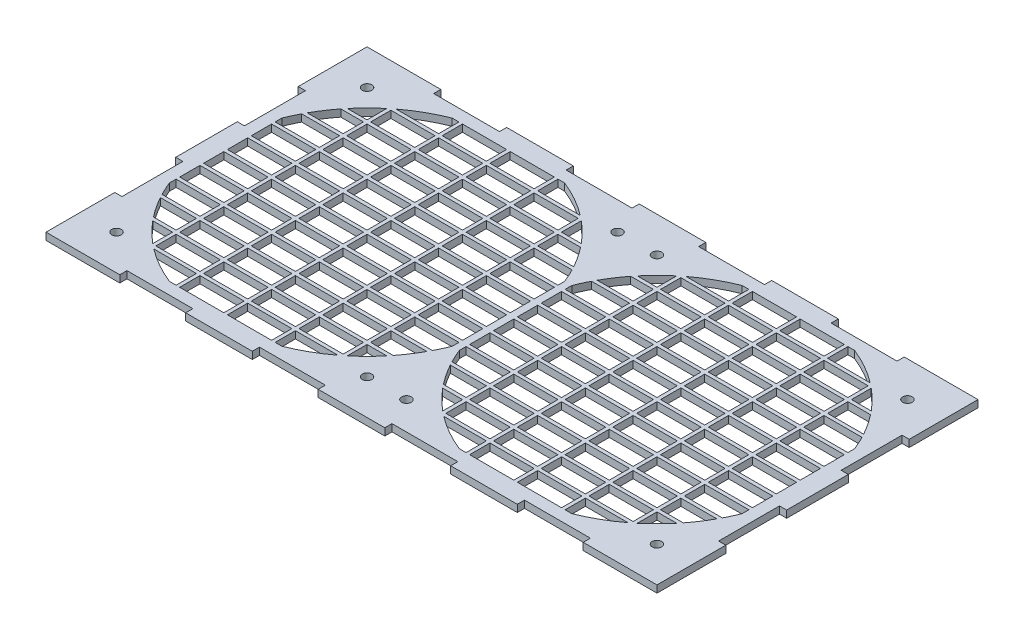
SolidWorks part; units mm, degrees
ref_plane "Front Plane" through (0, 0, 0) normal (0, 0, 1) x (1, 0, 0)
ref_plane "Top Plane" through (0, 0, 0) normal (0, 1, 0) x (1, 0, 0)
ref_plane "Right Plane" through (0, 0, 0) normal (1, 0, 0) x (0, 0, -1)
sketch "Sketch1" plane through (0, 0, 0) normal (0, 1, 0) x (1, 0, 0)
  line L0 (-60.65, 0) -> (0, 0) construction
  line L1 (0, 0) -> (60.65, 0) construction
  line L2 (-119.8, 23.5074) -> (-124.8, 23.5074) construction
  line L3 (-37.1426, -59.15) -> (-84.1574, -59.15)
  line L4 (-1.5, -23.5074) -> (-1.5, 23.5074)
  line L5 (-37.1426, 59.15) -> (-84.1574, 59.15)
  line L6 (-119.8, -23.5074) -> (-119.8, 23.5074)
  line L7 (-1.5, -59.15) -> (-119.8, 59.15) construction
  line L8 (-1.5, 59.15) -> (-119.8, -59.15) construction
  line L9 (84.1574, -59.15) -> (37.1426, -59.15)
  line L10 (119.8, -23.5074) -> (119.8, 23.5074)
  line L11 (84.1574, 59.15) -> (37.1426, 59.15)
  line L12 (1.5, -23.5074) -> (1.5, 23.5074)
  line L13 (119.8, -59.15) -> (1.5, 59.15) construction
  line L14 (119.8, 59.15) -> (1.5, -59.15) construction
  line L15 (96.9333, -64.15) -> (69.3667, -64.15)
  line L16 (124.8, -38.37) -> (124.8, -12.89)
  line L17 (96.9333, 64.15) -> (69.3667, 64.15)
  line L18 (-124.8, -38.37) -> (-124.8, -12.89)
  line L19 (124.8, -64.15) -> (-124.8, 64.15) construction
  line L20 (124.8, 64.15) -> (-132.4261, -68.07) construction
  line L21 (-84.1574, 64.15) -> (-84.1574, 59.15) construction
  line L22 (-69.3667, 64.15) -> (-96.9333, 64.15)
  line L25 (-124.8, 67.15) -> (-96.9333, 67.15)
  line L26 (-96.9333, 64.15) -> (-96.9333, 67.15)
  line L28 (-69.3667, 64.15) -> (-69.3667, 67.15)
  line L29 (-69.3667, 67.15) -> (-41.5, 67.15)
  line L30 (-41.5, 64.15) -> (-41.5, 67.15)
  line L32 (-13.9333, 64.15) -> (-13.9333, 67.15)
  line L33 (-13.9333, 67.15) -> (13.9333, 67.15)
  line L34 (13.9333, 64.15) -> (13.9333, 67.15)
  line L36 (41.5, 64.15) -> (41.5, 67.15)
  line L37 (41.5, 67.15) -> (69.3667, 67.15)
  line L38 (69.3667, 64.15) -> (69.3667, 67.15)
  line L41 (124.8, 67.15) -> (96.9333, 67.15)
  line L42 (96.9333, 64.15) -> (96.9333, 67.15)
  line L43 (-13.9333, 64.15) -> (-41.5, 64.15)
  line L44 (41.5, 64.15) -> (13.9333, 64.15)
  line L45 (-124.8, 65.65) -> (-97.2333, 65.65) construction
  line L46 (-97.2333, 65.65) -> (-96.9333, 65.65) construction
  line L47 (-69.3667, -64.15) -> (-96.9333, -64.15)
  line L50 (-124.8, -67.15) -> (-96.9333, -67.15)
  line L51 (-96.9333, -64.15) -> (-96.9333, -67.15)
  line L53 (-69.3667, -64.15) -> (-69.3667, -67.15)
  line L54 (-69.3667, -67.15) -> (-41.5, -67.15)
  line L55 (-41.5, -64.15) -> (-41.5, -67.15)
  line L57 (-13.9333, -64.15) -> (-13.9333, -67.15)
  line L58 (-13.9333, -67.15) -> (13.9333, -67.15)
  line L59 (13.9333, -64.15) -> (13.9333, -67.15)
  line L61 (41.5, -64.15) -> (41.5, -67.15)
  line L62 (41.5, -67.15) -> (69.3667, -67.15)
  line L63 (69.3667, -64.15) -> (69.3667, -67.15)
  line L65 (96.9333, -64.15) -> (96.9333, -67.15)
  line L66 (96.9333, -67.15) -> (124.8, -67.15)
  line L68 (-13.9333, -64.15) -> (-41.5, -64.15)
  line L69 (41.5, -64.15) -> (13.9333, -64.15)
  line L70 (-124.8, 64.15) -> (-124.8, 65.65) construction
  line L71 (-124.8, 67.15) -> (-127.8, 67.15)
  line L73 (-124.8, 38.37) -> (-127.8, 38.37)
  line L74 (-127.8, 67.15) -> (-127.8, 38.37)
  line L75 (-124.8, 12.89) -> (-127.8, 12.89)
  line L77 (-124.8, -12.89) -> (-127.8, -12.89)
  line L78 (-127.8, 12.89) -> (-127.8, -12.89)
  line L79 (-124.8, -67.15) -> (-127.8, -67.15)
  line L81 (-124.8, -38.37) -> (-127.8, -38.37)
  line L82 (-127.8, -67.15) -> (-127.8, -38.37)
  line L83 (124.8, -67.15) -> (127.8, -67.15)
  line L85 (124.8, -38.37) -> (127.8, -38.37)
  line L87 (124.8, -12.89) -> (127.8, -12.89)
  line L89 (124.8, 12.89) -> (127.8, 12.89)
  line L90 (127.8, -12.89) -> (127.8, 12.89)
  line L91 (124.8, 38.37) -> (127.8, 38.37)
  line L95 (-124.8, 65.65) -> (-124.8, 67.15) construction
  line L96 (-124.8, 12.89) -> (-124.8, 38.37)
  line L97 (124.8, 12.89) -> (124.8, 38.37)
  line L98 (124.8, 67.15) -> (127.8, 67.15)
  line L99 (-60.65, -64.15) -> (-60.65, -59.15) construction
  line L100 (124.8, 64.15) -> (124.8, 38.67) construction
  line L101 (124.8, 38.67) -> (124.8, 38.37) construction
  line L102 (127.8, 38.37) -> (127.8, 64.15)
  line L103 (127.8, 64.15) -> (127.8, 67.15)
  line L104 (124.8, 0) -> (119.8, 0) construction
  line L105 (127.8, -67.15) -> (127.8, -64.15)
  line L106 (127.8, -64.15) -> (127.8, -38.37)
  arc A1 (-119.8, -23.5074) -> (-84.1574, -59.15) centre (-60.65, 0) ccw
  arc A2 (-84.1574, 59.15) -> (-119.8, 23.5074) centre (-60.65, 0) ccw
  arc A3 (1.5, -23.5074) -> (37.1426, -59.15) centre (60.65, 0) ccw
  arc A4 (-1.5, 23.5074) -> (-37.1426, 59.15) centre (-60.65, 0) ccw
  arc A5 (37.1426, 59.15) -> (1.5, 23.5074) centre (60.65, 0) ccw
  arc A6 (119.8, 23.5074) -> (84.1574, 59.15) centre (60.65, 0) ccw
  arc A7 (84.1574, -59.15) -> (119.8, -23.5074) centre (60.65, 0) ccw
  arc A8 (-37.1426, -59.15) -> (-1.5, -23.5074) centre (-60.65, 0) ccw
  point P96 (124.8, -64.15)
  point P98 (0, 0)
  point P101 (124.8, 62.2393)
  point P103 (-127.8, -5.5733)
  point P104 (-127.8, -41.7742)
  dimension "D3" = 127.3
  dimension "D1" = 118.3
  dimension "D2" = 3
  dimension "D4" = 5
  dimension "D5" = 45
  dimension "D6" = 0.3
  dimension "D7" = 3
extrude "Boss-Extrude1" add sketch "Sketch1" along normal blind 3
sketch "Sketch2" plane through (0, 3, 0) normal (0, 1, 0) x (1, 0, 0)
  line L0 (-124.8, 38.37) -> (-124.8, 12.89) construction
  line L1 (-124.8, 60.65) -> (124.8, 60.65)
  line L2 (-124.8, 60.65) -> (-124.8, 59.15)
  line L3 (-124.8, 59.15) -> (124.8, 59.15)
  line L4 (124.8, 60.65) -> (124.8, 59.15)
  line L5 (124.8, 12.89) -> (124.8, 38.37) construction
  line L6 (-37.1426, 59.15) -> (-84.1574, 59.15) construction
  line L7 (-124.8, 50.6667) -> (-124.8, 49.1667)
  line L8 (-124.8, 50.6667) -> (124.8, 50.6667)
  line L9 (124.8, 50.6667) -> (124.8, 49.1667)
  line L10 (-124.8, 49.1667) -> (124.8, 49.1667)
  line L11 (-124.8, 40.6833) -> (-124.8, 39.1833)
  line L12 (-124.8, 40.6833) -> (124.8, 40.6833)
  line L13 (124.8, 40.6833) -> (124.8, 39.1833)
  line L14 (-124.8, 39.1833) -> (124.8, 39.1833)
  line L15 (-124.8, 30.7) -> (-124.8, 29.2)
  line L16 (-124.8, 30.7) -> (124.8, 30.7)
  line L17 (124.8, 30.7) -> (124.8, 29.2)
  line L18 (-124.8, 29.2) -> (124.8, 29.2)
  line L19 (-124.8, 20.7167) -> (-124.8, 19.2167)
  line L20 (-124.8, 20.7167) -> (124.8, 20.7167)
  line L21 (124.8, 20.7167) -> (124.8, 19.2167)
  line L22 (-124.8, 19.2167) -> (124.8, 19.2167)
  line L23 (-124.8, 10.7333) -> (-124.8, 9.2333)
  line L24 (-124.8, 10.7333) -> (124.8, 10.7333)
  line L25 (124.8, 10.7333) -> (124.8, 9.2333)
  line L26 (-124.8, 9.2333) -> (124.8, 9.2333)
  line L27 (-124.8, 0.75) -> (-124.8, -0.75)
  line L28 (-124.8, 0.75) -> (124.8, 0.75)
  line L29 (124.8, 0.75) -> (124.8, -0.75)
  line L30 (-124.8, -0.75) -> (124.8, -0.75)
  line L31 (-124.8, -9.2333) -> (-124.8, -10.7333)
  line L32 (-124.8, -9.2333) -> (124.8, -9.2333)
  line L33 (124.8, -9.2333) -> (124.8, -10.7333)
  line L34 (-124.8, -10.7333) -> (124.8, -10.7333)
  line L35 (-124.8, -19.2167) -> (-124.8, -20.7167)
  line L36 (-124.8, -19.2167) -> (124.8, -19.2167)
  line L37 (124.8, -19.2167) -> (124.8, -20.7167)
  line L38 (-124.8, -20.7167) -> (124.8, -20.7167)
  line L39 (-124.8, -29.2) -> (-124.8, -30.7)
  line L40 (-124.8, -29.2) -> (124.8, -29.2)
  line L41 (124.8, -29.2) -> (124.8, -30.7)
  line L42 (-124.8, -30.7) -> (124.8, -30.7)
  line L43 (-124.8, -39.1833) -> (-124.8, -40.6833)
  line L44 (-124.8, -39.1833) -> (124.8, -39.1833)
  line L45 (124.8, -39.1833) -> (124.8, -40.6833)
  line L46 (-124.8, -40.6833) -> (124.8, -40.6833)
  line L47 (-124.8, -49.1667) -> (-124.8, -50.6667)
  line L48 (-124.8, -49.1667) -> (124.8, -49.1667)
  line L49 (124.8, -49.1667) -> (124.8, -50.6667)
  line L50 (-124.8, -50.6667) -> (124.8, -50.6667)
  line L51 (-124.8, -59.15) -> (-124.8, -60.65)
  line L52 (-124.8, -59.15) -> (124.8, -59.15)
  line L53 (124.8, -59.15) -> (124.8, -60.65)
  line L54 (-124.8, -60.65) -> (124.8, -60.65)
  line L56 (-84.1574, -59.15) -> (-37.1426, -59.15) construction
  point P11 (-124.8, 59.15)
  point P59 (0, 0)
  dimension "D1" = 1.5
  dimension "D2" = 13
extrude "Boss-Extrude2" add sketch "Sketch2" against normal through all
sketch "Sketch3" plane through (0, 3, 0) normal (0, 1, 0) x (1, 0, 0)
  line L0 (0, 0) -> (0, 48.5777) construction
  line L1 (-119.8, 19.2167) -> (-119.8, 10.7333) construction
  line L2 (-119.8, -59.15) -> (-121.3, -59.15)
  line L3 (-119.8, -59.15) -> (-119.8, 59.15)
  line L4 (-119.8, 59.15) -> (-121.3, 59.15)
  line L5 (-121.3, -59.15) -> (-121.3, 59.15)
  line L6 (-37.1426, 59.15) -> (-84.1574, 59.15) construction
  line L7 (-84.1574, -59.15) -> (-37.1426, -59.15) construction
  line L8 (-99.8333, -59.15) -> (-99.8333, 59.15)
  line L9 (-99.8333, -59.15) -> (-101.3333, -59.15)
  line L10 (-101.3333, -59.15) -> (-101.3333, 59.15)
  line L11 (-99.8333, 59.15) -> (-101.3333, 59.15)
  line L12 (-79.8667, -59.15) -> (-79.8667, 59.15)
  line L13 (-79.8667, -59.15) -> (-81.3667, -59.15)
  line L14 (-81.3667, -59.15) -> (-81.3667, 59.15)
  line L15 (-79.8667, 59.15) -> (-81.3667, 59.15)
  line L16 (-59.9, -59.15) -> (-59.9, 59.15)
  line L17 (-59.9, -59.15) -> (-61.4, -59.15)
  line L18 (-61.4, -59.15) -> (-61.4, 59.15)
  line L19 (-59.9, 59.15) -> (-61.4, 59.15)
  line L20 (-39.9333, -59.15) -> (-39.9333, 59.15)
  line L21 (-39.9333, -59.15) -> (-41.4333, -59.15)
  line L22 (-41.4333, -59.15) -> (-41.4333, 59.15)
  line L23 (-39.9333, 59.15) -> (-41.4333, 59.15)
  line L24 (-19.9667, -59.15) -> (-19.9667, 59.15)
  line L25 (-19.9667, -59.15) -> (-21.4667, -59.15)
  line L26 (-21.4667, -59.15) -> (-21.4667, 59.15)
  line L27 (-19.9667, 59.15) -> (-21.4667, 59.15)
  line L28 (0, -59.15) -> (0, 59.15)
  line L29 (0, -59.15) -> (-1.5, -59.15)
  line L30 (-1.5, -59.15) -> (-1.5, 59.15)
  line L31 (0, 59.15) -> (-1.5, 59.15)
  line L48 (119.8, 59.15) -> (121.3, 59.15)
  line L49 (-1.5, -9.2333) -> (-1.5, -0.75) construction
  line L50 (121.3, -59.15) -> (121.3, 59.15)
  line L51 (119.8, -59.15) -> (121.3, -59.15)
  line L52 (119.8, -59.15) -> (119.8, 59.15)
  line L53 (-13.9333, -67.15) -> (13.9333, -67.15) construction
  line L54 (99.8333, 59.15) -> (101.3333, 59.15)
  line L55 (101.3333, -59.15) -> (101.3333, 59.15)
  line L56 (99.8333, -59.15) -> (101.3333, -59.15)
  line L57 (99.8333, -59.15) -> (99.8333, 59.15)
  line L58 (79.8667, 59.15) -> (81.3667, 59.15)
  line L59 (81.3667, -59.15) -> (81.3667, 59.15)
  line L60 (79.8667, -59.15) -> (81.3667, -59.15)
  line L61 (79.8667, -59.15) -> (79.8667, 59.15)
  line L62 (59.9, 59.15) -> (61.4, 59.15)
  line L63 (61.4, -59.15) -> (61.4, 59.15)
  line L64 (59.9, -59.15) -> (61.4, -59.15)
  line L65 (59.9, -59.15) -> (59.9, 59.15)
  line L66 (39.9333, 59.15) -> (41.4333, 59.15)
  line L67 (41.4333, -59.15) -> (41.4333, 59.15)
  line L68 (39.9333, -59.15) -> (41.4333, -59.15)
  line L69 (39.9333, -59.15) -> (39.9333, 59.15)
  line L70 (19.9667, 59.15) -> (21.4667, 59.15)
  line L71 (21.4667, -59.15) -> (21.4667, 59.15)
  line L72 (19.9667, -59.15) -> (21.4667, -59.15)
  line L73 (19.9667, -59.15) -> (19.9667, 59.15)
  line L74 (0, 59.15) -> (1.5, 59.15)
  line L75 (1.5, -59.15) -> (1.5, 59.15)
  line L76 (0, -59.15) -> (1.5, -59.15)
  line L77 (0, -59.15) -> (0, 59.15)
  line L78 (1.5, 19.2167) -> (1.5, 10.7333) construction
  point P45 (0, -67.15)
  dimension "D2" = 1.5
  dimension "D1" = 7
  dimension "D3" = 7
extrude "Boss-Extrude3" add sketch "Sketch3" against normal through all contours L28 L76 L75 L74 | L28 L31 L30 L29 | L24 L27 L26 L25 | L69 L68 L67 L66 | L16 L19 L18 L17 | L73 L70 L71 L72 | L65 L62 L63 L64 | L61 L58 L59 L60 | L55 L54 L57 L56 | L50 L48 L52 L51 | L20 L23 L22 L21 | L14 L15 L12 L13 | L10 L11 L8 L9 | L3 L4 L5 L2 region at (-60.65, 3, 0) region at (-20.7167, 3, 0) region at (-0.75, 3, 0) region at (0.75, 3, 0) region at (40.6833, 3, 0)
sketch "Sketch4" plane through (0, 3, 0) normal (0, 1, 0) x (1, 0, 0)
  line L1 (-113.05, 52.4) -> (-8.25, 52.4) construction
  line L2 (-113.05, 52.4) -> (-113.05, -52.4) construction
  line L3 (-113.05, -52.4) -> (-8.25, -52.4) construction
  line L4 (-8.25, 52.4) -> (-8.25, -52.4) construction
  line L5 (8.25, -52.4) -> (113.05, -52.4) construction
  line L6 (8.25, -52.4) -> (8.25, 52.4) construction
  line L7 (8.25, 52.4) -> (113.05, 52.4) construction
  line L8 (113.05, -52.4) -> (113.05, 52.4) construction
  line L9 (-8.25, 0) -> (0, 0) construction
  line L10 (0, 0) -> (8.25, 0) construction
  line L11 (61.4, 59.15) -> (59.9, 59.15) construction
  circle A0 centre (-113.05, 52.4) radius 2
  circle A1 centre (-8.25, 52.4) radius 2
  circle A2 centre (8.25, 52.4) radius 2
  circle A3 centre (113.05, 52.4) radius 2
  circle A4 centre (113.05, -52.4) radius 2
  circle A5 centre (8.25, -52.4) radius 2
  circle A6 centre (-8.25, -52.4) radius 2
  circle A7 centre (-113.05, -52.4) radius 2
  point P2 (8.25, 0)
  point P4 (-8.25, 0)
  point P8 (60.65, 52.4)
  point P23 (60.65, 59.15)
  point P28 (0, 0)
  point P29 (7.9847, -52.6653)
  dimension "D2" = 4
  dimension "D1" = 104.8
extrude "Cut-Extrude1" cut sketch "Sketch4" against normal through all
